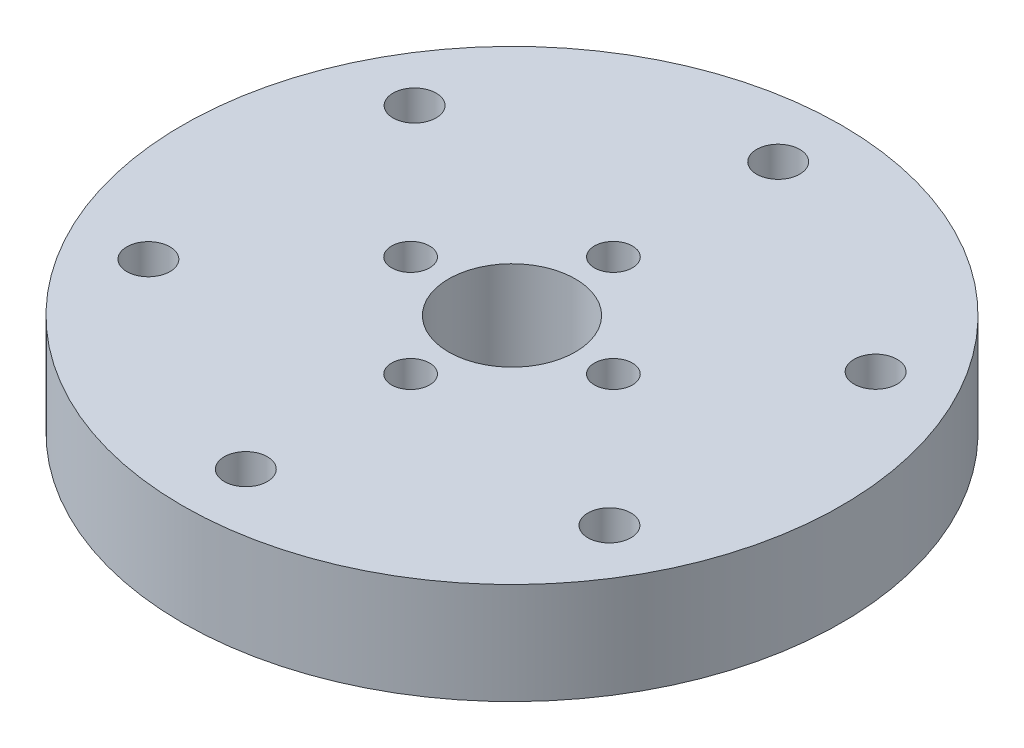
SolidWorks part; units mm, degrees
ref_plane "Front Plane" through (0, 0, 0) normal (0, 0, 1) x (1, 0, 0)
ref_plane "Top Plane" through (0, 0, 0) normal (0, 1, 0) x (1, 0, 0)
ref_plane "Right Plane" through (0, 0, 0) normal (1, 0, 0) x (0, 0, -1)
sketch "Sketch1" plane through (0, 0, 0) normal (0, 1, 0) x (1, 0, 0)
  line L0 (0, 0) -> (0, 21) construction
  line L1 (0, 0) -> (0, -8) construction
  circle A0 centre (0, 0) radius 26
  circle A1 centre (0, 0) radius 5
  circle A2 centre (0, 21) radius 1.7
  circle A3 centre (18.1865, 10.5) radius 1.7
  circle A4 centre (18.1865, -10.5) radius 1.7
  circle A5 centre (0, -21) radius 1.7
  circle A6 centre (-18.1865, -10.5) radius 1.7
  circle A7 centre (-18.1865, 10.5) radius 1.7
  circle A8 centre (0, -8) radius 1.5
  circle A9 centre (-8, 0) radius 1.5
  circle A10 centre (0, 8) radius 1.5
  circle A11 centre (8, 0) radius 1.5
  circle A12 centre (0, 21) radius 3.25
  circle A13 centre (18.1865, 10.5) radius 3.25
  circle A14 centre (18.1865, -10.5) radius 3.25
  circle A15 centre (0, -21) radius 3.25
  circle A16 centre (-18.1865, -10.5) radius 3.25
  circle A17 centre (-18.1865, 10.5) radius 3.25
  point P18 (0, 0)
  point P28 (0, 0)
  point P39 (0, 0)
  dimension "D1" = 52
  dimension "D2" = 10
  dimension "D4" = 3.4
  dimension "D7" = 3
  dimension "D9" = 6.5
  dimension "D3" = 21
  dimension "D6" = 8
  dimension "D5" = 6
  dimension "D8" = 4
  dimension "D10" = 6
extrude "Boss-Extrude1" add sketch "Sketch1" along normal blind 4.7 contours A0 A17 A16 A15 A14 A13 A12 A11 A10 A9 A8 A1 | A16 A6 | A15 A5 | A14 A4 | A17 A7 | A13 | A12 | A2 | A3 region at (-25.2646, 0, 0) region at (15.0285, 0, 10.5) region at (-3.1581, 0, 21) region at (-21.3446, 0, 10.5) region at (-21.3446, 0, -10.5)
extrude "Boss-Extrude2" add sketch "Sketch1<3>" against normal blind 3.3 contours A0 A17 A16 A15 A14 A13 A12 A11 A10 A9 A8 A1 region at (-25.2646, 0, 0)
sketch "Sketch1<3>" plane through (0, 0, 0) normal (0, 1, 0) x (1, 0, 0) same geometry as "Sketch1"
